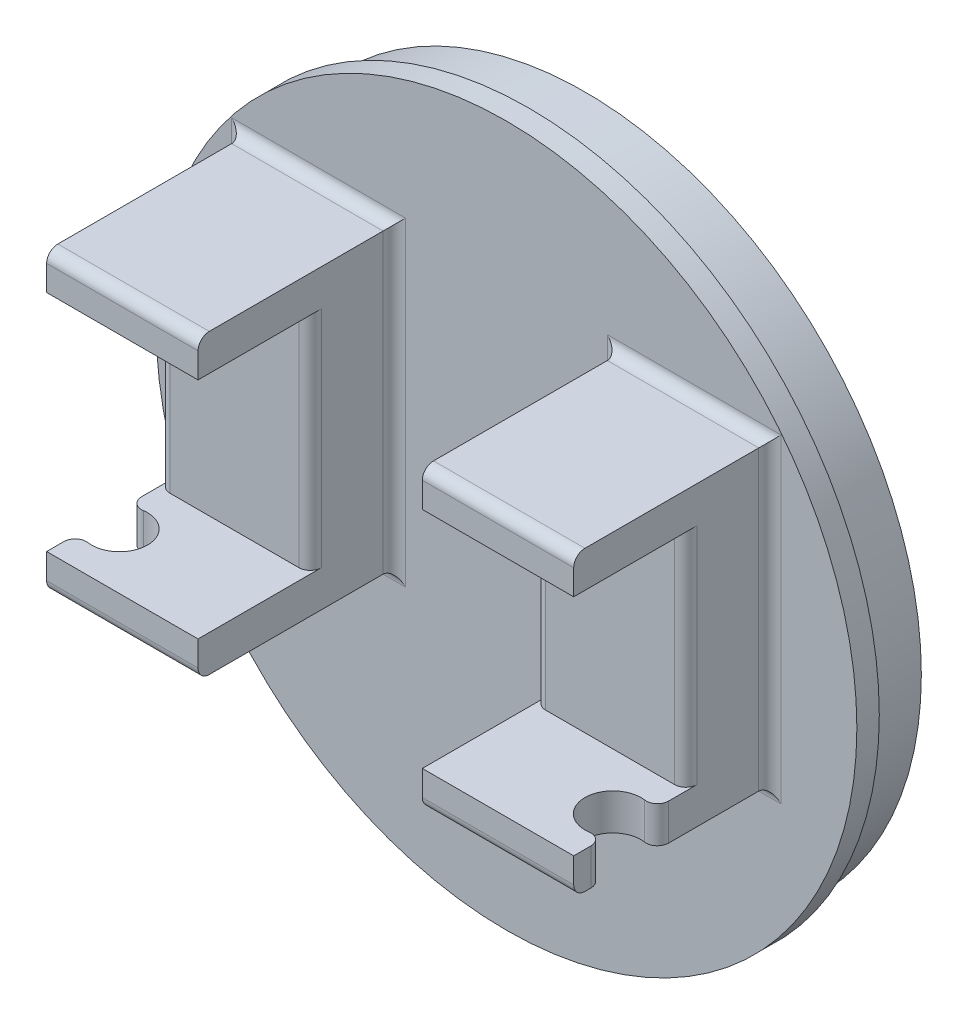
SolidWorks part; units mm, degrees
ref_plane "Piano frontale" through (0, 0, 0) normal (0, 0, 1) x (1, 0, 0)
ref_plane "Piano superiore" through (0, 0, 0) normal (0, 1, 0) x (1, 0, 0)
ref_plane "Piano destro" through (0, 0, 0) normal (1, 0, 0) x (0, 0, -1)
sketch "Sketch1" plane through (0, 0, 0) normal (0, 0, 1) x (1, 0, 0)
  circle A0 centre (0, 0) radius 62.5
  dimension "D1" = 125
extrude "Boss-Extrude1" add sketch "Sketch1" along normal blind 10
sketch "Sketch2" plane through (0, 0, 10) normal (0, 0, 1) x (1, 0, 0)
  circle A0 centre (0, 0) radius 62.5
  dimension "D1" = 125
extrude "Boss-Extrude2" add sketch "Sketch2" along normal blind 2
sketch "Sketch3" plane through (0, 0, 0) normal (0, 0, -1) x (-1, 0, 0)
  circle A0 centre (0, 0) radius 62.5
extrude "Boss-Extrude3" add sketch "Sketch3" along normal blind 2
sketch "Sketch4" plane through (0, 0, -2) normal (0, 0, -1) x (-1, 0, 0)
  circle A0 centre (0, 0) radius 16
  dimension "D1" = 32
extrude "Cut-Extrude1" cut sketch "Sketch4" against normal blind 10
sketch "Sketch7" plane through (0, 0, 12) normal (0, 0, 1) x (1, 0, 0)
  line L0 (0, 52.6548) -> (0, -52.6548) construction
  line L1 (-47, -10) -> (-20, -10)
  line L2 (-71.5289, 0) -> (71.5289, 0) construction
  line L3 (-47, -16.5) -> (-20, -16.5)
  line L4 (20, -16.5) -> (47, -16.5)
  line L5 (20, -10) -> (47, -10)
  line L6 (-20, -10) -> (-20, -16.5)
  line L8 (-47, -10) -> (-47, -16.5)
  line L9 (47, -10) -> (47, -16.5)
  line L10 (-47, 36.5) -> (-20, 36.5)
  line L11 (-20, 36.5) -> (-20, 30)
  line L12 (20, -10) -> (20, -16.5)
  line L13 (-47, 30) -> (-20, 30)
  line L14 (-47, 36.5) -> (-47, 30)
  line L15 (20, 36.5) -> (47, 36.5)
  line L16 (20, 36.5) -> (20, 30)
  line L17 (20, 30) -> (47, 30)
  line L18 (47, 36.5) -> (47, 30)
  point P4 (0, 0)
  point P6 (-15, 49.9017)
  point P7 (-15, -37.7306)
  point P8 (15, 49.9017)
  point P9 (15, -37.7306)
  point P10 (-15, -10)
  point P11 (-56.1745, -14)
  point P12 (15, -10)
  point P13 (-15, -14)
  point P14 (15, -14)
  point P15 (53.1786, -14)
  point P16 (-19, 49.9017)
  point P19 (-23, 49.9017)
  point P21 (0, 0)
  point P23 (-19, -59.542)
  point P29 (-23, -59.542)
  point P31 (23, 49.9017)
  point P32 (23, -59.542)
  dimension "D4" = 27
  dimension "D5" = 27
  dimension "D7" = 40
  dimension "D8" = 10
  dimension "D1" = 20
  dimension "D2" = 6.5
  dimension "D3" = 6.5
  dimension "D6" = 2
extrude "Boss-Extrude4" add sketch "Sketch7" along normal blind 35
sketch "Sketch8" plane through (0, -16.5, 0) normal (0, -1, 0) x (1, 0, 0)
  line L0 (0, 0) -> (0, 46.9577) construction
  line L1 (-47, 37) -> (-30.4458, 37) construction
  line L2 (-47, 47) -> (-47, 12) construction
  line L4 (-47, 47) -> (-20, 47) construction
  circle A0 centre (-44, 37) radius 5
  circle A1 centre (44, 37) radius 5
  dimension "D1" = 10
  dimension "D2" = 3
  dimension "D3" = 10
extrude "Cut-Extrude3" cut sketch "Sketch8" against normal blind 10
sketch "Sketch10" plane through (0, 0, 12) normal (0, 0, 1) x (1, 0, 0)
  line L0 (-47, 30) -> (-20, 30) construction
  line L1 (-47, 30) -> (-20, 30)
  line L2 (-20, -10) -> (-47, -10) construction
  line L3 (-20, -10) -> (-47, -10)
  line L4 (47, -10) -> (20, -10) construction
  line L5 (47, -10) -> (20, -10)
  line L6 (20, 30) -> (47, 30) construction
  line L7 (20, 30) -> (47, 30)
  line L8 (-47, 30) -> (-47, -10)
  line L9 (-20, 30) -> (-20, -10)
  line L10 (47, 30) -> (47, -10)
  line L11 (20, 30) -> (20, -10)
extrude "Boss-Extrude6" add sketch "Sketch10" along normal blind 15
fillet "Fillet3" radius 2 20 edges at (47, 10, 27) (20, 10, 27) (-47, 10, 12) (-33.5, -16.5, 12) (-20, 10, 12) (-33.5, -16.5, 47) (47, 10, 12) (20, 10, 12) (33.5, -16.5, 12) (33.5, -16.5, 47) (-33.5, 36.5, 12) (-33.5, 36.5, 47) (33.5, 36.5, 12) (33.5, 36.5, 47) (-47, -13.25, 41) (-47, -13.25, 33) (47, -13.25, 33) (47, -13.25, 41) (-47, 10, 27) (-20, 10, 27)
sketch "Sketch11" plane through (0, 0, 12) normal (0, 0, 1) x (1, 0, 0)
  circle A0 centre (0, 0) radius 2
  dimension "D1" = 4
extrude "Cut-Extrude4" cut sketch "Sketch11" against normal blind 15
sketch "Sketch12" plane through (0, 0, -2) normal (0, 0, -1) x (-1, 0, 0)
  line L0 (0, 0) -> (0, 81.355) construction
  line L1 (-95.3729, 0) -> (95.3729, 0) construction
  line L2 (-0.4619, 51.4477) -> (-1.4077, 53.731)
  line L3 (0.4619, 51.4477) -> (1.4077, 53.731)
  line L4 (-55.7923, 55) -> (55.7923, 55) construction
  line L5 (-1.9195, 54.9665) -> (0, 0) construction
  line L6 (0, 0) -> (1.9195, 54.9665) construction
  line L7 (4.0496, 51.2902) -> (5.1524, 53.5019)
  line L8 (3.128, 51.3546) -> (2.3438, 53.6983)
  line L9 (7.6176, 50.8827) -> (8.8719, 53.0122)
  line L10 (6.7027, 51.0113) -> (6.0839, 53.404)
  line L11 (11.1484, 50.2274) -> (12.5482, 52.2642)
  line L12 (10.2447, 50.4195) -> (9.7944, 52.8495)
  line L13 (14.625, 49.3274) -> (16.1634, 51.2615)
  line L14 (13.7369, 49.582) -> (13.4571, 52.0376)
  line L15 (18.0302, 48.187) -> (19.6999, 50.0091)
  line L16 (17.1621, 48.503) -> (17.0543, 50.9721)
  line L17 (21.3477, 46.8119) -> (23.1404, 48.5131)
  line L18 (20.5037, 47.1877) -> (20.5684, 49.6583)
  line L19 (24.5611, 45.2088) -> (26.4681, 46.7808)
  line L20 (23.7454, 45.6425) -> (23.9822, 48.1025)
  line L21 (27.6549, 43.3853) -> (29.6669, 44.8205)
  line L22 (26.8714, 43.8749) -> (27.2793, 46.3124)
  line L23 (30.6139, 41.3505) -> (32.7211, 42.6418)
  line L24 (29.8665, 41.8936) -> (30.4434, 44.2967)
  line L25 (33.4238, 39.1143) -> (35.616, 40.2555)
  line L26 (32.7161, 39.7082) -> (33.4592, 42.0652)
  line L27 (36.0709, 36.6875) -> (38.3373, 37.673)
  line L28 (35.4063, 37.3293) -> (36.3121, 39.6287)
  line L29 (38.5422, 34.0819) -> (40.8718, 34.9069)
  line L30 (37.924, 34.7685) -> (38.988, 36.9992)
  line L31 (40.8257, 31.3104) -> (43.2073, 31.9708)
  line L32 (40.2569, 32.0384) -> (41.4739, 34.1894)
  line L33 (42.9104, 28.3862) -> (45.3322, 28.8789)
  line L34 (42.3938, 29.1522) -> (43.7578, 31.213)
  line L35 (44.786, 25.3238) -> (47.2362, 25.6464)
  line L36 (44.324, 26.1239) -> (45.8285, 28.0846)
  line L37 (46.4434, 22.138) -> (48.9102, 22.2889)
  line L38 (46.0384, 22.9684) -> (47.676, 24.8193)
  line L39 (47.8745, 18.8443) -> (50.3458, 18.8228)
  line L40 (47.5284, 19.701) -> (49.2912, 21.4332)
  line L41 (49.0724, 15.4589) -> (51.5362, 15.265)
  line L42 (48.7869, 16.3375) -> (50.6662, 17.9426)
  line L43 (50.0312, 11.9981) -> (52.4755, 11.6328)
  line L44 (49.8077, 12.8945) -> (51.7944, 14.3646)
  line L45 (50.7463, 8.4789) -> (53.1591, 7.944)
  line L46 (50.5859, 9.3887) -> (52.6702, 10.7166)
  line L47 (51.2142, 4.9183) -> (53.5838, 4.2164)
  line L48 (51.1176, 5.8372) -> (53.2895, 7.0164)
  line L49 (51.4325, 1.3338) -> (53.7474, 0.4683)
  line L50 (51.4002, 2.2572) -> (53.6491, 3.282)
  line L51 (51.4002, -2.2572) -> (53.6491, -3.282)
  line L52 (51.4325, -1.3338) -> (53.7474, -0.4683)
  line L53 (51.1176, -5.8372) -> (53.2895, -7.0164)
  line L54 (51.2142, -4.9183) -> (53.5838, -4.2164)
  line L55 (50.5859, -9.3887) -> (52.6702, -10.7166)
  line L56 (50.7463, -8.4789) -> (53.1591, -7.944)
  line L57 (49.8077, -12.8945) -> (51.7944, -14.3646)
  line L58 (50.0312, -11.9981) -> (52.4755, -11.6328)
  line L59 (48.7869, -16.3375) -> (50.6662, -17.9426)
  line L60 (49.0724, -15.4589) -> (51.5362, -15.265)
  line L61 (47.5284, -19.701) -> (49.2912, -21.4332)
  line L62 (47.8745, -18.8443) -> (50.3458, -18.8228)
  line L63 (46.0384, -22.9684) -> (47.676, -24.8193)
  line L64 (46.4434, -22.138) -> (48.9102, -22.2889)
  line L65 (44.324, -26.1239) -> (45.8285, -28.0846)
  line L66 (44.786, -25.3238) -> (47.2362, -25.6464)
  line L67 (42.3938, -29.1522) -> (43.7578, -31.213)
  line L68 (42.9104, -28.3862) -> (45.3322, -28.8789)
  line L69 (40.2569, -32.0384) -> (41.4739, -34.1894)
  line L70 (40.8257, -31.3104) -> (43.2073, -31.9708)
  line L71 (37.924, -34.7685) -> (38.988, -36.9992)
  line L72 (38.5422, -34.0819) -> (40.8718, -34.9069)
  line L73 (35.4063, -37.3293) -> (36.3121, -39.6287)
  line L74 (36.0709, -36.6875) -> (38.3373, -37.673)
  line L75 (32.7161, -39.7082) -> (33.4592, -42.0652)
  line L76 (33.4238, -39.1143) -> (35.616, -40.2555)
  line L77 (29.8665, -41.8936) -> (30.4434, -44.2967)
  line L78 (30.6139, -41.3505) -> (32.7211, -42.6418)
  line L79 (26.8714, -43.8749) -> (27.2793, -46.3124)
  line L80 (27.6549, -43.3853) -> (29.6669, -44.8205)
  line L81 (23.7454, -45.6425) -> (23.9822, -48.1025)
  line L82 (24.5611, -45.2088) -> (26.4681, -46.7808)
  line L83 (20.5037, -47.1877) -> (20.5684, -49.6583)
  line L84 (21.3477, -46.8119) -> (23.1404, -48.5131)
  line L85 (17.1621, -48.503) -> (17.0543, -50.9721)
  line L86 (18.0302, -48.187) -> (19.6999, -50.0091)
  line L87 (13.7369, -49.582) -> (13.4571, -52.0376)
  line L88 (14.625, -49.3274) -> (16.1634, -51.2615)
  line L89 (10.2447, -50.4195) -> (9.7944, -52.8495)
  line L90 (11.1484, -50.2274) -> (12.5482, -52.2642)
  line L91 (6.7027, -51.0113) -> (6.0839, -53.404)
  line L92 (7.6176, -50.8827) -> (8.8719, -53.0122)
  line L93 (3.128, -51.3546) -> (2.3438, -53.6983)
  line L94 (4.0496, -51.2902) -> (5.1524, -53.5019)
  line L95 (-0.4619, -51.4477) -> (-1.4077, -53.731)
  line L96 (0.4619, -51.4477) -> (1.4077, -53.731)
  line L97 (-4.0496, -51.2902) -> (-5.1524, -53.5019)
  line L98 (-3.128, -51.3546) -> (-2.3438, -53.6983)
  line L99 (-7.6176, -50.8827) -> (-8.8719, -53.0122)
  line L100 (-6.7027, -51.0113) -> (-6.0839, -53.404)
  line L101 (-11.1484, -50.2274) -> (-12.5482, -52.2642)
  line L102 (-10.2447, -50.4195) -> (-9.7944, -52.8495)
  line L103 (-14.625, -49.3274) -> (-16.1634, -51.2615)
  line L104 (-13.7369, -49.582) -> (-13.4571, -52.0376)
  line L105 (-18.0302, -48.187) -> (-19.6999, -50.0091)
  line L106 (-17.1621, -48.503) -> (-17.0543, -50.9721)
  line L107 (-21.3477, -46.8119) -> (-23.1404, -48.5131)
  line L108 (-20.5037, -47.1877) -> (-20.5684, -49.6583)
  line L109 (-24.5611, -45.2088) -> (-26.4681, -46.7808)
  line L110 (-23.7454, -45.6425) -> (-23.9822, -48.1025)
  line L111 (-27.6549, -43.3853) -> (-29.6669, -44.8205)
  line L112 (-26.8714, -43.8749) -> (-27.2793, -46.3124)
  line L113 (-30.6139, -41.3505) -> (-32.7211, -42.6418)
  line L114 (-29.8665, -41.8936) -> (-30.4434, -44.2967)
  line L115 (-33.4238, -39.1143) -> (-35.616, -40.2555)
  line L116 (-32.7161, -39.7082) -> (-33.4592, -42.0652)
  line L117 (-36.0709, -36.6875) -> (-38.3373, -37.673)
  line L118 (-35.4063, -37.3293) -> (-36.3121, -39.6287)
  line L119 (-38.5422, -34.0819) -> (-40.8718, -34.9069)
  line L120 (-37.924, -34.7685) -> (-38.988, -36.9992)
  line L121 (-40.8257, -31.3104) -> (-43.2073, -31.9708)
  line L122 (-40.2569, -32.0384) -> (-41.4739, -34.1894)
  line L123 (-42.9104, -28.3862) -> (-45.3322, -28.8789)
  line L124 (-42.3938, -29.1522) -> (-43.7578, -31.213)
  line L125 (-44.786, -25.3238) -> (-47.2362, -25.6464)
  line L126 (-44.324, -26.1239) -> (-45.8285, -28.0846)
  line L127 (-46.4434, -22.138) -> (-48.9102, -22.2889)
  line L128 (-46.0384, -22.9684) -> (-47.676, -24.8193)
  line L129 (-47.8745, -18.8443) -> (-50.3458, -18.8228)
  line L130 (-47.5284, -19.701) -> (-49.2912, -21.4332)
  line L131 (-49.0724, -15.4589) -> (-51.5362, -15.265)
  line L132 (-48.7869, -16.3375) -> (-50.6662, -17.9426)
  line L133 (-50.0312, -11.9981) -> (-52.4755, -11.6328)
  line L134 (-49.8077, -12.8945) -> (-51.7944, -14.3646)
  line L135 (-50.7463, -8.4789) -> (-53.1591, -7.944)
  line L136 (-50.5859, -9.3887) -> (-52.6702, -10.7166)
  line L137 (-51.2142, -4.9183) -> (-53.5838, -4.2164)
  line L138 (-51.1176, -5.8372) -> (-53.2895, -7.0164)
  line L139 (-51.4325, -1.3338) -> (-53.7474, -0.4683)
  line L140 (-51.4002, -2.2572) -> (-53.6491, -3.282)
  line L141 (-51.4002, 2.2572) -> (-53.6491, 3.282)
  line L142 (-51.4325, 1.3338) -> (-53.7474, 0.4683)
  line L143 (-51.1176, 5.8372) -> (-53.2895, 7.0164)
  line L144 (-51.2142, 4.9183) -> (-53.5838, 4.2164)
  line L145 (-50.5859, 9.3887) -> (-52.6702, 10.7166)
  line L146 (-50.7463, 8.4789) -> (-53.1591, 7.944)
  line L147 (-49.8077, 12.8945) -> (-51.7944, 14.3646)
  line L148 (-50.0312, 11.9981) -> (-52.4755, 11.6328)
  line L149 (-48.7869, 16.3375) -> (-50.6662, 17.9426)
  line L150 (-49.0724, 15.4589) -> (-51.5362, 15.265)
  line L151 (-47.5284, 19.701) -> (-49.2912, 21.4332)
  line L152 (-47.8745, 18.8443) -> (-50.3458, 18.8228)
  line L153 (-46.0384, 22.9684) -> (-47.676, 24.8193)
  line L154 (-46.4434, 22.138) -> (-48.9102, 22.2889)
  line L155 (-44.324, 26.1239) -> (-45.8285, 28.0846)
  line L156 (-44.786, 25.3238) -> (-47.2362, 25.6464)
  line L157 (-42.3938, 29.1522) -> (-43.7578, 31.213)
  line L158 (-42.9104, 28.3862) -> (-45.3322, 28.8789)
  line L159 (-40.2569, 32.0384) -> (-41.4739, 34.1894)
  line L160 (-40.8257, 31.3104) -> (-43.2073, 31.9708)
  line L161 (-37.924, 34.7685) -> (-38.988, 36.9992)
  line L162 (-38.5422, 34.0819) -> (-40.8718, 34.9069)
  line L163 (-35.4063, 37.3293) -> (-36.3121, 39.6287)
  line L164 (-36.0709, 36.6875) -> (-38.3373, 37.673)
  line L165 (-32.7161, 39.7082) -> (-33.4592, 42.0652)
  line L166 (-33.4238, 39.1143) -> (-35.616, 40.2555)
  line L167 (-29.8665, 41.8936) -> (-30.4434, 44.2967)
  line L168 (-30.6139, 41.3505) -> (-32.7211, 42.6418)
  line L169 (-26.8714, 43.8749) -> (-27.2793, 46.3124)
  line L170 (-27.6549, 43.3853) -> (-29.6669, 44.8205)
  line L171 (-23.7454, 45.6425) -> (-23.9822, 48.1025)
  line L172 (-24.5611, 45.2088) -> (-26.4681, 46.7808)
  line L173 (-20.5037, 47.1877) -> (-20.5684, 49.6583)
  line L174 (-21.3477, 46.8119) -> (-23.1404, 48.5131)
  line L175 (-17.1621, 48.503) -> (-17.0543, 50.9721)
  line L176 (-18.0302, 48.187) -> (-19.6999, 50.0091)
  line L177 (-13.7369, 49.582) -> (-13.4571, 52.0376)
  line L178 (-14.625, 49.3274) -> (-16.1634, 51.2615)
  line L179 (-10.2447, 50.4195) -> (-9.7944, 52.8495)
  line L180 (-11.1484, 50.2274) -> (-12.5482, 52.2642)
  line L181 (-6.7027, 51.0113) -> (-6.0839, 53.404)
  line L182 (-7.6176, 50.8827) -> (-8.8719, 53.0122)
  line L183 (-3.128, 51.3546) -> (-2.3438, 53.6983)
  line L184 (-4.0496, 51.2902) -> (-5.1524, 53.5019)
  arc A0 (-16.1634, -51.2615) -> (-17.0543, -50.9721) centre (-16.5547, -50.9503) cw
  arc A1 (-0.4619, 51.4477) -> (0.4619, 51.4477) centre (0, 51.639) ccw
  arc A2 (3.128, 51.3546) -> (4.0496, 51.2902) centre (3.6022, 51.5133) ccw
  arc A3 (6.7027, 51.0113) -> (7.6176, 50.8827) centre (7.1868, 51.1365) ccw
  arc A4 (10.2447, 50.4195) -> (11.1484, 50.2274) centre (10.7364, 50.5106) ccw
  arc A5 (13.7369, 49.582) -> (14.625, 49.3274) centre (14.2336, 49.6386) ccw
  arc A6 (17.1621, 48.503) -> (18.0302, 48.187) centre (17.6616, 48.5248) ccw
  arc A7 (20.5037, 47.1877) -> (21.3477, 46.8119) centre (21.0035, 47.1746) ccw
  arc A8 (23.7454, 45.6425) -> (24.5611, 45.2088) centre (24.2431, 45.5946) ccw
  arc A9 (26.8714, 43.8749) -> (27.6549, 43.3853) centre (27.3645, 43.7924) ccw
  arc A10 (29.8665, 41.8936) -> (30.6139, 41.3505) centre (30.3527, 41.7769) ccw
  arc A11 (32.7161, 39.7082) -> (33.4238, 39.1143) centre (33.1929, 39.5578) ccw
  arc A12 (35.4063, 37.3293) -> (36.0709, 36.6875) centre (35.8715, 37.146) ccw
  arc A13 (37.924, 34.7685) -> (38.5422, 34.0819) centre (38.3753, 34.5533) ccw
  arc A14 (40.2569, 32.0384) -> (40.8257, 31.3104) centre (40.6921, 31.7922) ccw
  arc A15 (42.3938, 29.1522) -> (42.9104, 28.3862) centre (42.8107, 28.8762) ccw
  arc A16 (44.324, 26.1239) -> (44.786, 25.3238) centre (44.7207, 25.8195) ccw
  arc A17 (46.0384, 22.9684) -> (46.4434, 22.138) centre (46.4129, 22.6371) ccw
  arc A18 (47.5284, 19.701) -> (47.8745, 18.8443) centre (47.8789, 19.3443) ccw
  arc A19 (48.7869, 16.3375) -> (49.0724, 15.4589) centre (49.1116, 15.9573) ccw
  arc A20 (49.8077, 12.8945) -> (50.0312, 11.9981) centre (50.1051, 12.4926) ccw
  arc A21 (50.5859, 9.3887) -> (50.7463, 8.4789) centre (50.8545, 8.967) ccw
  arc A22 (51.1176, 5.8372) -> (51.2142, 4.9183) centre (51.3562, 5.3977) ccw
  arc A23 (51.4002, 2.2572) -> (51.4325, 1.3338) centre (51.6076, 1.8022) ccw
  arc A24 (51.4325, -1.3338) -> (51.4002, -2.2572) centre (51.6076, -1.8022) ccw
  arc A25 (51.2142, -4.9183) -> (51.1176, -5.8372) centre (51.3562, -5.3977) ccw
  arc A26 (50.7463, -8.4789) -> (50.5859, -9.3887) centre (50.8545, -8.967) ccw
  arc A27 (50.0312, -11.9981) -> (49.8077, -12.8945) centre (50.1051, -12.4926) ccw
  arc A28 (49.0724, -15.4589) -> (48.7869, -16.3375) centre (49.1116, -15.9573) ccw
  arc A29 (47.8745, -18.8443) -> (47.5284, -19.701) centre (47.8789, -19.3443) ccw
  arc A30 (46.4434, -22.138) -> (46.0384, -22.9684) centre (46.4129, -22.6371) ccw
  arc A31 (44.786, -25.3238) -> (44.324, -26.1239) centre (44.7207, -25.8195) ccw
  arc A32 (42.9104, -28.3862) -> (42.3938, -29.1522) centre (42.8107, -28.8762) ccw
  arc A33 (40.8257, -31.3104) -> (40.2569, -32.0384) centre (40.6921, -31.7922) ccw
  arc A34 (38.5422, -34.0819) -> (37.924, -34.7685) centre (38.3753, -34.5533) ccw
  arc A35 (36.0709, -36.6875) -> (35.4063, -37.3293) centre (35.8715, -37.146) ccw
  arc A36 (33.4238, -39.1143) -> (32.7161, -39.7082) centre (33.1929, -39.5578) ccw
  arc A37 (30.6139, -41.3505) -> (29.8665, -41.8936) centre (30.3527, -41.7769) ccw
  arc A38 (27.6549, -43.3853) -> (26.8714, -43.8749) centre (27.3645, -43.7924) ccw
  arc A39 (24.5611, -45.2088) -> (23.7454, -45.6425) centre (24.2431, -45.5946) ccw
  arc A40 (21.3477, -46.8119) -> (20.5037, -47.1877) centre (21.0035, -47.1746) ccw
  arc A41 (18.0302, -48.187) -> (17.1621, -48.503) centre (17.6616, -48.5248) ccw
  arc A42 (14.625, -49.3274) -> (13.7369, -49.582) centre (14.2336, -49.6386) ccw
  arc A43 (11.1484, -50.2274) -> (10.2447, -50.4195) centre (10.7364, -50.5106) ccw
  arc A44 (7.6176, -50.8827) -> (6.7027, -51.0113) centre (7.1868, -51.1365) ccw
  arc A45 (4.0496, -51.2902) -> (3.128, -51.3546) centre (3.6022, -51.5133) ccw
  arc A46 (0.4619, -51.4477) -> (-0.4619, -51.4477) centre (0, -51.639) ccw
  arc A47 (-3.128, -51.3546) -> (-4.0496, -51.2902) centre (-3.6022, -51.5133) ccw
  arc A48 (-6.7027, -51.0113) -> (-7.6176, -50.8827) centre (-7.1868, -51.1365) ccw
  arc A49 (-10.2447, -50.4195) -> (-11.1484, -50.2274) centre (-10.7364, -50.5106) ccw
  arc A50 (-13.7369, -49.582) -> (-14.625, -49.3274) centre (-14.2336, -49.6386) ccw
  arc A51 (-17.1621, -48.503) -> (-18.0302, -48.187) centre (-17.6616, -48.5248) ccw
  arc A52 (-20.5037, -47.1877) -> (-21.3477, -46.8119) centre (-21.0035, -47.1746) ccw
  arc A53 (-23.7454, -45.6425) -> (-24.5611, -45.2088) centre (-24.2431, -45.5946) ccw
  arc A54 (-26.8714, -43.8749) -> (-27.6549, -43.3853) centre (-27.3645, -43.7924) ccw
  arc A55 (-29.8665, -41.8936) -> (-30.6139, -41.3505) centre (-30.3527, -41.7769) ccw
  arc A56 (-32.7161, -39.7082) -> (-33.4238, -39.1143) centre (-33.1929, -39.5578) ccw
  arc A57 (-35.4063, -37.3293) -> (-36.0709, -36.6875) centre (-35.8715, -37.146) ccw
  arc A58 (-37.924, -34.7685) -> (-38.5422, -34.0819) centre (-38.3753, -34.5533) ccw
  arc A59 (-40.2569, -32.0384) -> (-40.8257, -31.3104) centre (-40.6921, -31.7922) ccw
  arc A60 (-42.3938, -29.1522) -> (-42.9104, -28.3862) centre (-42.8107, -28.8762) ccw
  arc A61 (-44.324, -26.1239) -> (-44.786, -25.3238) centre (-44.7207, -25.8195) ccw
  arc A62 (-46.0384, -22.9684) -> (-46.4434, -22.138) centre (-46.4129, -22.6371) ccw
  arc A63 (-47.5284, -19.701) -> (-47.8745, -18.8443) centre (-47.8789, -19.3443) ccw
  arc A64 (-48.7869, -16.3375) -> (-49.0724, -15.4589) centre (-49.1116, -15.9573) ccw
  arc A65 (-49.8077, -12.8945) -> (-50.0312, -11.9981) centre (-50.1051, -12.4926) ccw
  arc A66 (-50.5859, -9.3887) -> (-50.7463, -8.4789) centre (-50.8545, -8.967) ccw
  arc A67 (-51.1176, -5.8372) -> (-51.2142, -4.9183) centre (-51.3562, -5.3977) ccw
  arc A68 (-51.4002, -2.2572) -> (-51.4325, -1.3338) centre (-51.6076, -1.8022) ccw
  arc A69 (-51.4325, 1.3338) -> (-51.4002, 2.2572) centre (-51.6076, 1.8022) ccw
  arc A70 (-51.2142, 4.9183) -> (-51.1176, 5.8372) centre (-51.3562, 5.3977) ccw
  arc A71 (-50.7463, 8.4789) -> (-50.5859, 9.3887) centre (-50.8545, 8.967) ccw
  arc A72 (-50.0312, 11.9981) -> (-49.8077, 12.8945) centre (-50.1051, 12.4926) ccw
  arc A73 (-49.0724, 15.4589) -> (-48.7869, 16.3375) centre (-49.1116, 15.9573) ccw
  arc A74 (-47.8745, 18.8443) -> (-47.5284, 19.701) centre (-47.8789, 19.3443) ccw
  arc A75 (-46.4434, 22.138) -> (-46.0384, 22.9684) centre (-46.4129, 22.6371) ccw
  arc A76 (-44.786, 25.3238) -> (-44.324, 26.1239) centre (-44.7207, 25.8195) ccw
  arc A77 (-42.9104, 28.3862) -> (-42.3938, 29.1522) centre (-42.8107, 28.8762) ccw
  arc A78 (-40.8257, 31.3104) -> (-40.2569, 32.0384) centre (-40.6921, 31.7922) ccw
  arc A79 (-38.5422, 34.0819) -> (-37.924, 34.7685) centre (-38.3753, 34.5533) ccw
  arc A80 (-36.0709, 36.6875) -> (-35.4063, 37.3293) centre (-35.8715, 37.146) ccw
  arc A81 (-33.4238, 39.1143) -> (-32.7161, 39.7082) centre (-33.1929, 39.5578) ccw
  arc A82 (-30.6139, 41.3505) -> (-29.8665, 41.8936) centre (-30.3527, 41.7769) ccw
  arc A83 (-27.6549, 43.3853) -> (-26.8714, 43.8749) centre (-27.3645, 43.7924) ccw
  arc A84 (-24.5611, 45.2088) -> (-23.7454, 45.6425) centre (-24.2431, 45.5946) ccw
  arc A85 (-21.3477, 46.8119) -> (-20.5037, 47.1877) centre (-21.0035, 47.1746) ccw
  arc A86 (-18.0302, 48.187) -> (-17.1621, 48.503) centre (-17.6616, 48.5248) ccw
  arc A87 (-14.625, 49.3274) -> (-13.7369, 49.582) centre (-14.2336, 49.6386) ccw
  arc A88 (-11.1484, 50.2274) -> (-10.2447, 50.4195) centre (-10.7364, 50.5106) ccw
  arc A89 (-7.6176, 50.8827) -> (-6.7027, 51.0113) centre (-7.1868, 51.1365) ccw
  arc A90 (-4.0496, 51.2902) -> (-3.128, 51.3546) centre (-3.6022, 51.5133) ccw
  arc A91 (-12.5482, -52.2642) -> (-13.4571, -52.0376) centre (-12.9603, -51.9809) cw
  arc A92 (-8.8719, -53.0122) -> (-9.7944, -52.8495) centre (-9.3027, -52.7584) cw
  arc A93 (-5.1524, -53.5019) -> (-6.0839, -53.404) centre (-5.5998, -53.2788) cw
  arc A94 (-1.4077, -53.731) -> (-2.3438, -53.6983) centre (-1.8696, -53.5396) cw
  arc A95 (2.3438, -53.6983) -> (1.4077, -53.731) centre (1.8696, -53.5396) cw
  arc A96 (6.0839, -53.404) -> (5.1524, -53.5019) centre (5.5998, -53.2788) cw
  arc A97 (9.7944, -52.8495) -> (8.8719, -53.0122) centre (9.3027, -52.7584) cw
  arc A98 (13.4571, -52.0376) -> (12.5482, -52.2642) centre (12.9603, -51.9809) cw
  arc A99 (17.0543, -50.9721) -> (16.1634, -51.2615) centre (16.5547, -50.9503) cw
  arc A100 (-23.9822, 48.1025) -> (-23.1404, 48.5131) centre (-23.4845, 48.1504) cw
  arc A101 (-27.2793, 46.3124) -> (-26.4681, 46.7808) centre (-26.7861, 46.395) cw
  arc A102 (-38.988, 36.9992) -> (-38.3373, 37.673) centre (-38.5367, 37.2144) cw
  arc A103 (-41.4739, 34.1894) -> (-40.8718, 34.9069) centre (-41.0387, 34.4356) cw
  arc A104 (-43.7578, 31.213) -> (-43.2073, 31.9708) centre (-43.3409, 31.489) cw
  arc A105 (-45.8285, 28.0846) -> (-45.3322, 28.8789) centre (-45.4319, 28.389) cw
  arc A106 (-47.676, 24.8193) -> (-47.2362, 25.6464) centre (-47.3015, 25.1507) cw
  arc A107 (-49.2912, 21.4332) -> (-48.9102, 22.2889) centre (-48.9407, 21.7898) cw
  arc A108 (-50.6662, 17.9426) -> (-50.3458, 18.8228) centre (-50.3415, 18.3228) cw
  arc A109 (-51.7944, 14.3646) -> (-51.5362, 15.265) centre (-51.497, 14.7665) cw
  arc A110 (-52.6702, 10.7166) -> (-52.4755, 11.6328) centre (-52.4016, 11.1383) cw
  arc A111 (-53.2895, 7.0164) -> (-53.1591, 7.944) centre (-53.0509, 7.4558) cw
  arc A112 (-53.6491, 3.282) -> (-53.5838, 4.2164) centre (-53.4418, 3.737) cw
  arc A113 (-53.7474, -0.4683) -> (-53.7474, 0.4683) centre (-53.5723, 0) cw
  arc A114 (-53.5838, -4.2164) -> (-53.6491, -3.282) centre (-53.4418, -3.737) cw
  arc A115 (-53.1591, -7.944) -> (-53.2895, -7.0164) centre (-53.0509, -7.4558) cw
  arc A116 (-52.4755, -11.6328) -> (-52.6702, -10.7166) centre (-52.4016, -11.1383) cw
  arc A117 (-51.5362, -15.265) -> (-51.7944, -14.3646) centre (-51.497, -14.7665) cw
  arc A118 (-50.3458, -18.8228) -> (-50.6662, -17.9426) centre (-50.3415, -18.3228) cw
  arc A119 (-48.9102, -22.2889) -> (-49.2912, -21.4332) centre (-48.9407, -21.7898) cw
  arc A120 (-47.2362, -25.6464) -> (-47.676, -24.8193) centre (-47.3015, -25.1507) cw
  arc A121 (-45.3322, -28.8789) -> (-45.8285, -28.0846) centre (-45.4319, -28.389) cw
  arc A122 (-43.2073, -31.9708) -> (-43.7578, -31.213) centre (-43.3409, -31.489) cw
  arc A123 (-40.8718, -34.9069) -> (-41.4739, -34.1894) centre (-41.0387, -34.4356) cw
  arc A124 (-38.3373, -37.673) -> (-38.988, -36.9992) centre (-38.5367, -37.2144) cw
  arc A125 (-35.616, -40.2555) -> (-36.3121, -39.6287) centre (-35.8468, -39.812) cw
  arc A126 (-32.7211, -42.6418) -> (-33.4592, -42.0652) centre (-32.9824, -42.2155) cw
  arc A127 (-29.6669, -44.8205) -> (-30.4434, -44.2967) centre (-29.9572, -44.4134) cw
  arc A128 (-26.4681, -46.7808) -> (-27.2793, -46.3124) centre (-26.7861, -46.395) cw
  arc A129 (-23.1404, -48.5131) -> (-23.9822, -48.1025) centre (-23.4845, -48.1504) cw
  arc A130 (-19.6999, -50.0091) -> (-20.5684, -49.6583) centre (-20.0685, -49.6713) cw
  arc A131 (20.5684, -49.6583) -> (19.6999, -50.0091) centre (20.0685, -49.6713) cw
  arc A132 (23.9822, -48.1025) -> (23.1404, -48.5131) centre (23.4845, -48.1504) cw
  arc A133 (27.2793, -46.3124) -> (26.4681, -46.7808) centre (26.7861, -46.395) cw
  arc A134 (30.4434, -44.2967) -> (29.6669, -44.8205) centre (29.9572, -44.4134) cw
  arc A135 (33.4592, -42.0652) -> (32.7211, -42.6418) centre (32.9824, -42.2155) cw
  arc A136 (36.3121, -39.6287) -> (35.616, -40.2555) centre (35.8468, -39.812) cw
  arc A137 (38.988, -36.9992) -> (38.3373, -37.673) centre (38.5367, -37.2144) cw
  arc A138 (41.4739, -34.1894) -> (40.8718, -34.9069) centre (41.0387, -34.4356) cw
  arc A139 (43.7578, -31.213) -> (43.2073, -31.9708) centre (43.3409, -31.489) cw
  arc A140 (45.8285, -28.0846) -> (45.3322, -28.8789) centre (45.4319, -28.389) cw
  arc A141 (47.676, -24.8193) -> (47.2362, -25.6464) centre (47.3015, -25.1507) cw
  arc A142 (49.2912, -21.4332) -> (48.9102, -22.2889) centre (48.9407, -21.7898) cw
  arc A143 (50.6662, -17.9426) -> (50.3458, -18.8228) centre (50.3415, -18.3228) cw
  arc A144 (51.7944, -14.3646) -> (51.5362, -15.265) centre (51.497, -14.7665) cw
  arc A145 (52.6702, -10.7166) -> (52.4755, -11.6328) centre (52.4016, -11.1383) cw
  arc A146 (53.2895, -7.0164) -> (53.1591, -7.944) centre (53.0509, -7.4558) cw
  arc A147 (53.6491, -3.282) -> (53.5838, -4.2164) centre (53.4418, -3.737) cw
  arc A148 (53.7474, 0.4683) -> (53.7474, -0.4683) centre (53.5723, 0) cw
  arc A149 (53.5838, 4.2164) -> (53.6491, 3.282) centre (53.4418, 3.737) cw
  arc A150 (53.1591, 7.944) -> (53.2895, 7.0164) centre (53.0509, 7.4558) cw
  arc A151 (52.4755, 11.6328) -> (52.6702, 10.7166) centre (52.4016, 11.1383) cw
  arc A152 (51.5362, 15.265) -> (51.7944, 14.3646) centre (51.497, 14.7665) cw
  arc A153 (50.3458, 18.8228) -> (50.6662, 17.9426) centre (50.3415, 18.3228) cw
  arc A154 (48.9102, 22.2889) -> (49.2912, 21.4332) centre (48.9407, 21.7898) cw
  arc A155 (47.2362, 25.6464) -> (47.676, 24.8193) centre (47.3015, 25.1507) cw
  arc A156 (45.3322, 28.8789) -> (45.8285, 28.0846) centre (45.4319, 28.389) cw
  arc A157 (43.2073, 31.9708) -> (43.7578, 31.213) centre (43.3409, 31.489) cw
  arc A158 (40.8718, 34.9069) -> (41.4739, 34.1894) centre (41.0387, 34.4356) cw
  arc A159 (38.3373, 37.673) -> (38.988, 36.9992) centre (38.5367, 37.2144) cw
  arc A160 (35.616, 40.2555) -> (36.3121, 39.6287) centre (35.8468, 39.812) cw
  arc A161 (32.7211, 42.6418) -> (33.4592, 42.0652) centre (32.9824, 42.2155) cw
  arc A162 (29.6669, 44.8205) -> (30.4434, 44.2967) centre (29.9572, 44.4134) cw
  arc A163 (26.4681, 46.7808) -> (27.2793, 46.3124) centre (26.7861, 46.395) cw
  arc A164 (23.1404, 48.5131) -> (23.9822, 48.1025) centre (23.4845, 48.1504) cw
  arc A165 (19.6999, 50.0091) -> (20.5684, 49.6583) centre (20.0685, 49.6713) cw
  arc A166 (16.1634, 51.2615) -> (17.0543, 50.9721) centre (16.5547, 50.9503) cw
  arc A167 (12.5482, 52.2642) -> (13.4571, 52.0376) centre (12.9603, 51.9809) cw
  arc A168 (8.8719, 53.0122) -> (9.7944, 52.8495) centre (9.3027, 52.7584) cw
  arc A169 (5.1524, 53.5019) -> (6.0839, 53.404) centre (5.5998, 53.2788) cw
  circle A170 centre (0, 0) radius 22.5
  arc A171 (-30.4434, 44.2967) -> (-29.6669, 44.8205) centre (-29.9572, 44.4134) cw
  arc A172 (-33.4592, 42.0652) -> (-32.7211, 42.6418) centre (-32.9824, 42.2155) cw
  arc A173 (-36.3121, 39.6287) -> (-35.616, 40.2555) centre (-35.8468, 39.812) cw
  arc A174 (-20.5684, 49.6583) -> (-19.6999, 50.0091) centre (-20.0685, 49.6713) cw
  arc A175 (-17.0543, 50.9721) -> (-16.1634, 51.2615) centre (-16.5547, 50.9503) cw
  arc A176 (-13.4571, 52.0376) -> (-12.5482, 52.2642) centre (-12.9603, 51.9809) cw
  arc A177 (-9.7944, 52.8495) -> (-8.8719, 53.0122) centre (-9.3027, 52.7584) cw
  arc A178 (-6.0839, 53.404) -> (-5.1524, 53.5019) centre (-5.5998, 53.2788) cw
  arc A179 (1.4077, 53.731) -> (2.3438, 53.6983) centre (1.8696, 53.5396) cw
  arc A180 (-1.4077, 53.731) -> (-2.3438, 53.6983) centre (-1.8696, 53.5396) ccw
  point P5 (0, 0)
  point P15 (0, 50.3325)
  point P463 (0, 0)
  dimension "D1" = 0.5
  dimension "D2" = 0.5
  dimension "D4" = 45
  dimension "D3" = 90
  dimension "D5" = 4
extrude "Cut-Extrude5" cut sketch "Sketch12" against normal blind 10
sketch "Sketch13" plane through (0, 0, -2) normal (0, 0, -1) x (-1, 0, 0)
  circle A0 centre (0, 0) radius 62.5 construction
  circle A1 centre (0, 0) radius 62.5
  circle A2 centre (0, 0) radius 60
  dimension "D1" = 2.5
extrude "Cut-Extrude6" cut sketch "Sketch13" against normal blind 10
